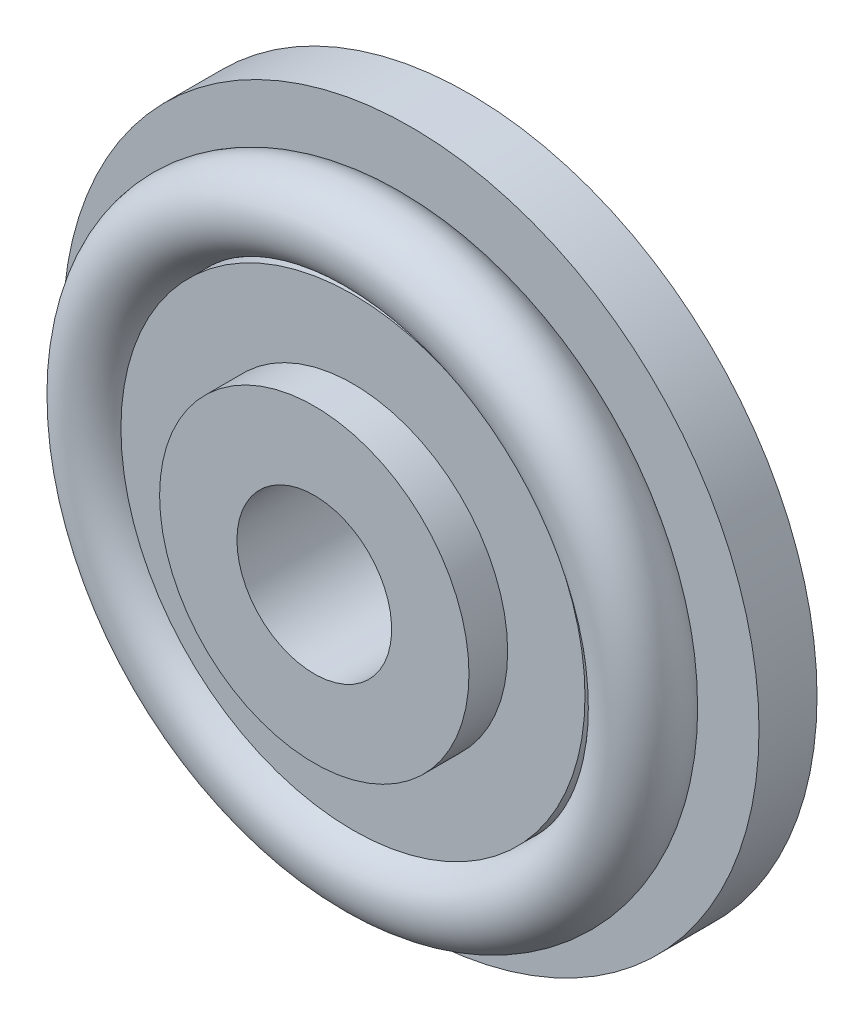
SolidWorks part; units mm, degrees
material "1060 合金"
ref_plane "前视基准面" through (0, 0, 0) normal (0, 0, 1) x (1, 0, 0)
ref_plane "上视基准面" through (0, 0, 0) normal (0, 1, 0) x (1, 0, 0)
ref_plane "右视基准面" through (0, 0, 0) normal (1, 0, 0) x (0, 0, -1)
sketch "草图1" plane through (0, 0, 0) normal (0, 1, 0) x (1, 0, 0)
  line L0 (0, 0) -> (0, 9.0028) construction
  line L1 (0, 8) -> (18, 8)
  line L2 (18, 8) -> (18, 5)
  line L3 (18, 5) -> (12, 5)
  line L4 (12, 5) -> (12, 2)
  line L5 (12, 2) -> (8, 2)
  line L6 (8, 2) -> (8, 0)
  line L7 (8, 0) -> (0, 0)
  line L8 (0, 8) -> (0, 0)
  dimension "D1" = 2
  dimension "D2" = 8
  dimension "D3" = 12
  dimension "D4" = 6
  dimension "D5" = 3
  dimension "D6" = 3
revolve "旋转1" add sketch "草图1" angle 360 about L0
hole_wizard "Ø10.0 (10) 直径孔1" positions "草图6" profile "草图5" hole size "Ø10.0" standard "GB" end condition through all
sketch "草图6" plane through (0, 0, -8) normal (0, 0, -1) x (-1, 0, 0)
  point P0 (0, 0)
sketch "草图5" plane through (0, 0, -8) normal (1, 0, 0) x (0, 1, 0)
  line L0 (0, 0) -> (0, 8)
  line L1 (0, 8) -> (4, 8)
  line L2 (4, 8) -> (4, 0)
  line L5 (4, 0) -> (0, 0)
  line L11 (0, -6.35) -> (0, 107.95) construction
  dimension "通孔孔直径" = 8
  dimension "通孔孔深度" = 8
sketch "草图7" plane through (0, 0, 0) normal (0, 1, 0) x (1, 0, 0)
  line L0 (12, 2) -> (12, 5) construction
  line L1 (12, 2) -> (12, 5) construction
  line L2 (-18, 5) -> (18, 5) construction
  circle A0 centre (14, 3) radius 2
  dimension "D1" = 4
revolve "旋转2" add sketch "草图7" angle 360 about axis through (0, 0, 0) along (0, 0, 1)
